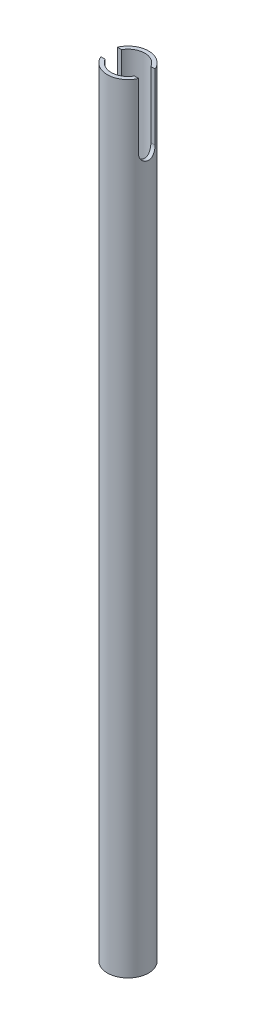
SolidWorks part; units mm, degrees
material "AISI 4130 Steel, annealed at 865C"
ref_plane "X-Y Datum" through (0, 0, 0) normal (0, 0, 1) x (1, 0, 0)
ref_plane "X-Z Datum" through (0, 0, 0) normal (0, 1, 0) x (1, 0, 0)
ref_plane "Y-Z Datum" through (0, 0, 0) normal (1, 0, 0) x (0, 0, -1)
sketch "Sketch1" plane through (0, 0, 0) normal (0, 1, 0) x (1, 0, 0)
  circle A0 centre (0, 0) radius 7.9375
  circle A1 centre (0, 0) radius 6.4643
  dimension "D1" = 1.4732
  dimension "D2" = 15.875
extrude "Boss-Extrude1" add sketch "Sketch1" along normal offset from surface (299.825 mm away) 25.4 offset beyond the face yes
sketch "Sketch2" plane through (0, 0, 0) normal (1, 0, 0) x (0, 0, -1)
  line L0 (3.175, 299.825) -> (3.175, 274.425)
  line L1 (7.9375, 299.825) -> (-7.9375, 299.825) construction
  line L2 (-3.175, 274.425) -> (-3.175, 299.825)
  line L3 (-3.175, 299.825) -> (3.175, 299.825)
  line L4 (7.9375, 0) -> (7.9375, 299.825) construction
  arc A0 (3.175, 274.425) -> (-3.175, 274.425) centre (0, 274.425) cw
  dimension "D1" = 6.35
  dimension "D2" = 25.4
  dimension "D3" = 4.7625
extrude "Cut-Extrude1" cut sketch "Sketch2" against normal blind 9.525 and the other way blind 9.525
